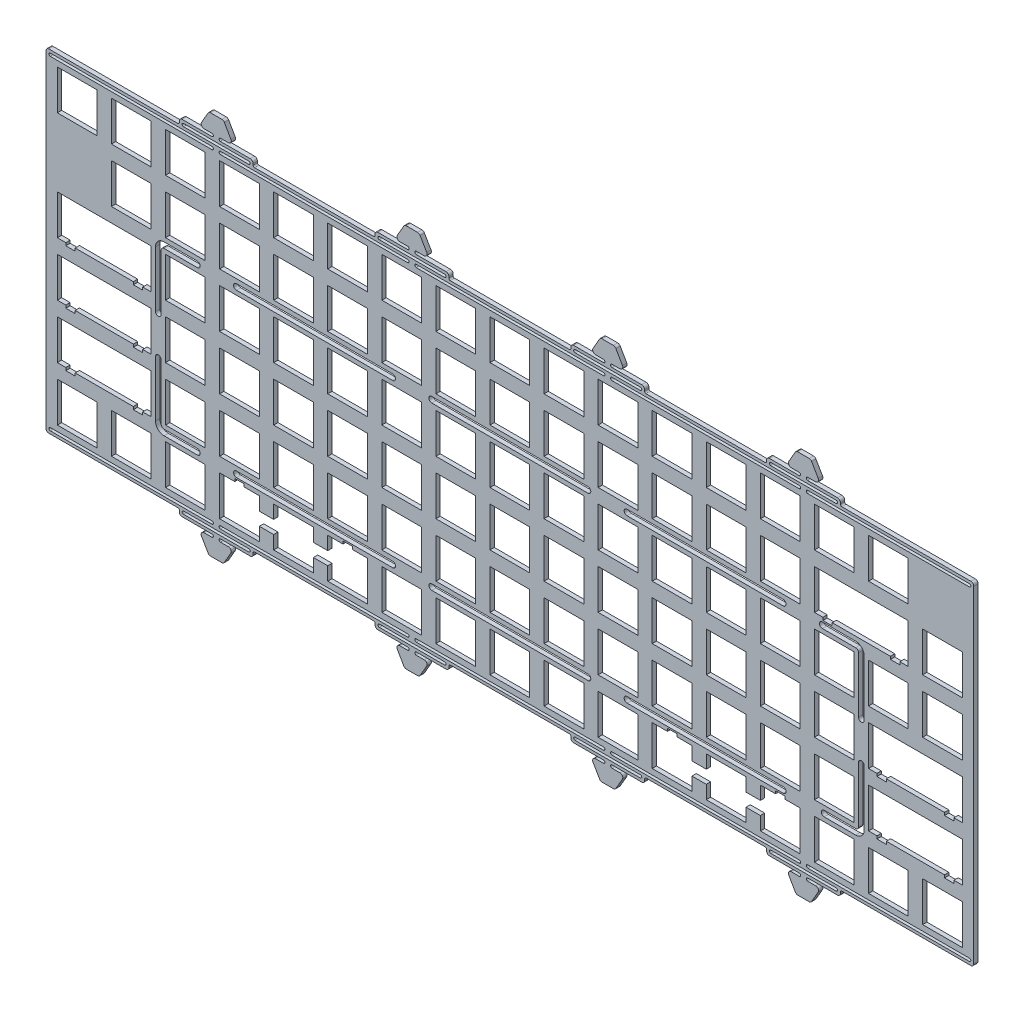
SolidWorks part; units mm, degrees
material "Acrylic (Medium-high impact)"
ref_plane "Front Plane" through (0, 0, 0) normal (0, 0, 1) x (1, 0, 0)
ref_plane "Top Plane" through (0, 0, 0) normal (0, 1, 0) x (1, 0, 0)
ref_plane "Right Plane" through (0, 0, 0) normal (1, 0, 0) x (0, 0, -1)
sketch "Sketch2" plane through (0, 0, 0) normal (0, 0, 1) x (1, 0, 0)
  line L0 (102.249, -54.6242) -> (102.249, -40.6233)
  line L1 (102.249, -40.6233) -> (96.9, -40.6233)
  line L2 (96.9, -40.6233) -> (96.9, -39.6546)
  line L3 (96.9, -39.6546) -> (93.6, -39.6546)
  line L4 (93.6, -39.6546) -> (93.6, -40.6233)
  line L5 (93.6, -40.6233) -> (88.25, -40.6233)
  line L6 (88.25, -40.6233) -> (88.25, -45.3238)
  line L7 (88.25, -45.3238) -> (83.199, -45.3238)
  line L8 (83.199, -45.3238) -> (83.199, -40.6233)
  line L9 (83.199, -40.6233) -> (69.2, -40.6233)
  line L10 (69.2, -40.6233) -> (69.2, -45.3238)
  line L11 (69.2, -45.3238) -> (64.149, -45.3238)
  line L12 (64.149, -45.3238) -> (64.149, -40.6233)
  line L13 (64.149, -40.6233) -> (58.801, -40.6233)
  line L14 (58.801, -40.6233) -> (58.801, -39.6546)
  line L15 (58.801, -39.6546) -> (55.5, -39.6546)
  line L16 (55.5, -39.6546) -> (55.5, -40.6233)
  line L17 (55.5, -40.6233) -> (50.15, -40.6233)
  line L18 (50.15, -40.6233) -> (50.15, -54.6242)
  line L19 (50.15, -54.6242) -> (64.149, -54.6242)
  line L20 (64.149, -54.6242) -> (64.149, -49.9223)
  line L21 (64.149, -49.9223) -> (69.2, -49.9223)
  line L22 (69.2, -49.9223) -> (69.2, -54.6242)
  line L23 (69.2, -54.6242) -> (83.199, -54.6242)
  line L24 (83.199, -54.6242) -> (83.199, -49.9223)
  line L25 (83.199, -49.9223) -> (88.25, -49.9223)
  line L26 (88.25, -49.9223) -> (88.25, -54.6242)
  line L27 (88.25, -54.6242) -> (102.249, -54.6242)
  line L28 (-50.1496, -54.6242) -> (-50.1496, -40.6233)
  line L29 (-50.1496, -40.6233) -> (-55.4991, -40.6233)
  line L30 (-55.4991, -40.6233) -> (-55.4991, -39.6546)
  line L31 (-55.4991, -39.6546) -> (-58.7994, -39.6546)
  line L32 (-58.7994, -39.6546) -> (-58.7994, -40.6233)
  line L33 (-58.7994, -40.6233) -> (-64.1503, -40.6233)
  line L34 (-64.1503, -40.6233) -> (-64.1503, -45.3238)
  line L35 (-64.1503, -45.3238) -> (-69.201, -45.3238)
  line L36 (-69.201, -45.3238) -> (-69.201, -40.6233)
  line L37 (-69.201, -40.6233) -> (-83.2003, -40.6233)
  line L38 (-83.2003, -40.6233) -> (-83.2003, -45.3238)
  line L39 (-83.2003, -45.3238) -> (-88.2496, -45.3238)
  line L40 (-88.2496, -45.3238) -> (-88.2496, -40.6233)
  line L41 (-88.2496, -40.6233) -> (-93.6003, -40.6233)
  line L42 (-93.6003, -40.6233) -> (-93.6003, -39.6546)
  line L43 (-93.6003, -39.6546) -> (-96.9003, -39.6546)
  line L44 (-96.9003, -39.6546) -> (-96.9003, -40.6233)
  line L45 (-96.9003, -40.6233) -> (-102.2503, -40.6233)
  line L46 (-102.2503, -40.6233) -> (-102.2503, -54.6242)
  line L47 (-102.2503, -54.6242) -> (-88.2496, -54.6242)
  line L48 (-88.2496, -54.6242) -> (-88.2496, -49.9223)
  line L49 (-88.2496, -49.9223) -> (-83.2003, -49.9223)
  line L50 (-83.2003, -49.9223) -> (-83.2003, -54.6242)
  line L51 (-83.2003, -54.6242) -> (-69.201, -54.6242)
  line L52 (-69.201, -54.6242) -> (-69.201, -49.9223)
  line L53 (-69.201, -49.9223) -> (-64.1503, -49.9223)
  line L54 (-64.1503, -49.9223) -> (-64.1503, -54.6242)
  line L55 (-64.1503, -54.6242) -> (-50.1496, -54.6242)
  line L56 (145.4, -40.6233) -> (159.399, -40.6233)
  line L57 (159.399, -40.6233) -> (159.399, -54.6242)
  line L58 (159.399, -54.6242) -> (145.4, -54.6242)
  line L59 (145.4, -54.6242) -> (145.4, -40.6233)
  line L60 (126.35, -40.6233) -> (140.349, -40.6233)
  line L61 (140.349, -40.6233) -> (140.349, -54.6242)
  line L62 (140.349, -54.6242) -> (126.35, -54.6242)
  line L63 (126.35, -54.6242) -> (126.35, -40.6233)
  line L64 (107.3, -40.6233) -> (121.299, -40.6233)
  line L65 (121.299, -40.6233) -> (121.299, -54.6242)
  line L66 (121.299, -54.6242) -> (107.3, -54.6242)
  line L67 (107.3, -54.6242) -> (107.3, -40.6233)
  line L68 (31.1, -40.6233) -> (45.099, -40.6233)
  line L69 (45.099, -40.6233) -> (45.099, -54.6242)
  line L70 (45.099, -54.6242) -> (31.1, -54.6242)
  line L71 (31.1, -54.6242) -> (31.1, -40.6233)
  line L72 (12.05, -40.6233) -> (26.049, -40.6233)
  line L73 (26.049, -40.6233) -> (26.049, -54.6242)
  line L74 (26.049, -54.6242) -> (12.05, -54.6242)
  line L75 (12.05, -54.6242) -> (12.05, -40.6233)
  line L76 (-7, -40.6233) -> (6.999, -40.6233)
  line L77 (6.999, -40.6233) -> (6.999, -54.6242)
  line L78 (6.999, -54.6242) -> (-7, -54.6242)
  line L79 (-7, -54.6242) -> (-7, -40.6233)
  line L80 (-26.05, -40.6233) -> (-12.051, -40.6233)
  line L81 (-12.051, -40.6233) -> (-12.051, -54.6242)
  line L82 (-12.051, -54.6242) -> (-26.05, -54.6242)
  line L83 (-26.05, -54.6242) -> (-26.05, -40.6233)
  line L84 (-45.102, -40.6233) -> (-31.101, -40.6233)
  line L85 (-31.101, -40.6233) -> (-31.101, -54.6242)
  line L86 (-31.101, -54.6242) -> (-45.102, -54.6242)
  line L87 (-45.102, -54.6242) -> (-45.102, -40.6233)
  line L88 (-121.3003, -40.6233) -> (-107.301, -40.6233)
  line L89 (-107.301, -40.6233) -> (-107.301, -54.6242)
  line L90 (-107.301, -54.6242) -> (-121.3003, -54.6242)
  line L91 (-121.3003, -54.6242) -> (-121.3003, -40.6233)
  line L92 (-140.3503, -40.6233) -> (-126.351, -40.6233)
  line L93 (-126.351, -40.6233) -> (-126.351, -54.6242)
  line L94 (-126.351, -54.6242) -> (-140.3503, -54.6242)
  line L95 (-140.3503, -54.6242) -> (-140.3503, -40.6233)
  line L96 (-159.4004, -40.6233) -> (-145.4008, -40.6233)
  line L97 (-145.4008, -40.6233) -> (-145.4008, -54.6242)
  line L98 (-145.4008, -54.6242) -> (-159.4004, -54.6242)
  line L99 (-159.4004, -54.6242) -> (-159.4004, -40.6233)
  line L100 (126.35, -21.5748) -> (126.35, -35.5742)
  line L101 (126.35, -35.5742) -> (129.325, -35.5742)
  line L102 (129.325, -35.5742) -> (129.325, -36.5443)
  line L103 (129.325, -36.5443) -> (132.624, -36.5443)
  line L104 (132.624, -36.5443) -> (132.624, -35.5742)
  line L105 (132.624, -35.5742) -> (153.125, -35.5742)
  line L106 (153.125, -35.5742) -> (153.125, -36.5443)
  line L107 (153.125, -36.5443) -> (156.424, -36.5443)
  line L108 (156.424, -36.5443) -> (156.424, -35.5742)
  line L109 (156.424, -35.5742) -> (159.399, -35.5742)
  line L110 (159.399, -35.5742) -> (159.399, -21.5748)
  line L111 (159.399, -21.5748) -> (126.35, -21.5748)
  line L112 (-159.4004, -21.5748) -> (-159.4004, -35.5742)
  line L113 (-159.4004, -35.5742) -> (-156.4252, -35.5742)
  line L114 (-156.4252, -35.5742) -> (-156.4252, -36.5443)
  line L115 (-156.4252, -36.5443) -> (-153.1262, -36.5443)
  line L116 (-153.1262, -36.5443) -> (-153.1262, -35.5742)
  line L117 (-153.1262, -35.5742) -> (-132.6251, -35.5742)
  line L118 (-132.6251, -35.5742) -> (-132.6251, -36.5443)
  line L119 (-132.6251, -36.5443) -> (-129.326, -36.5443)
  line L120 (-129.326, -36.5443) -> (-129.326, -35.5742)
  line L121 (-129.326, -35.5742) -> (-126.351, -35.5742)
  line L122 (-126.351, -35.5742) -> (-126.351, -21.5748)
  line L123 (-126.351, -21.5748) -> (-159.4004, -21.5748)
  line L124 (107.3, -21.5748) -> (121.299, -21.5748)
  line L125 (121.299, -21.5748) -> (121.299, -35.5742)
  line L126 (121.299, -35.5742) -> (107.3, -35.5742)
  line L127 (107.3, -35.5742) -> (107.3, -21.5748)
  line L128 (88.25, -21.5748) -> (102.249, -21.5748)
  line L129 (102.249, -21.5748) -> (102.249, -35.5742)
  line L130 (102.249, -35.5742) -> (88.25, -35.5742)
  line L131 (88.25, -35.5742) -> (88.25, -21.5748)
  line L132 (69.2, -21.5748) -> (83.199, -21.5748)
  line L133 (83.199, -21.5748) -> (83.199, -35.5742)
  line L134 (83.199, -35.5742) -> (69.2, -35.5742)
  line L135 (69.2, -35.5742) -> (69.2, -21.5748)
  line L136 (50.15, -21.5748) -> (64.149, -21.5748)
  line L137 (64.149, -21.5748) -> (64.149, -35.5742)
  line L138 (64.149, -35.5742) -> (50.15, -35.5742)
  line L139 (50.15, -35.5742) -> (50.15, -21.5748)
  line L140 (31.1, -21.5748) -> (45.099, -21.5748)
  line L141 (45.099, -21.5748) -> (45.099, -35.5742)
  line L142 (45.099, -35.5742) -> (31.1, -35.5742)
  line L143 (31.1, -35.5742) -> (31.1, -21.5748)
  line L144 (12.05, -21.5748) -> (26.049, -21.5748)
  line L145 (26.049, -21.5748) -> (26.049, -35.5742)
  line L146 (26.049, -35.5742) -> (12.05, -35.5742)
  line L147 (12.05, -35.5742) -> (12.05, -21.5748)
  line L148 (-7, -21.5748) -> (6.999, -21.5748)
  line L149 (6.999, -21.5748) -> (6.999, -35.5742)
  line L150 (6.999, -35.5742) -> (-7, -35.5742)
  line L151 (-7, -35.5742) -> (-7, -21.5748)
  line L152 (-26.05, -21.5748) -> (-12.051, -21.5748)
  line L153 (-12.051, -21.5748) -> (-12.051, -35.5742)
  line L154 (-12.051, -35.5742) -> (-26.05, -35.5742)
  line L155 (-26.05, -35.5742) -> (-26.05, -21.5748)
  line L156 (-45.102, -21.5748) -> (-31.101, -21.5748)
  line L157 (-31.101, -21.5748) -> (-31.101, -35.5742)
  line L158 (-31.101, -35.5742) -> (-45.102, -35.5742)
  line L159 (-45.102, -35.5742) -> (-45.102, -21.5748)
  line L160 (-64.1517, -21.5748) -> (-50.151, -21.5748)
  line L161 (-50.151, -21.5748) -> (-50.151, -35.5742)
  line L162 (-50.151, -35.5742) -> (-64.1517, -35.5742)
  line L163 (-64.1517, -35.5742) -> (-64.1517, -21.5748)
  line L164 (-83.2003, -21.5748) -> (-69.201, -21.5748)
  line L165 (-69.201, -21.5748) -> (-69.201, -35.5742)
  line L166 (-69.201, -35.5742) -> (-83.2003, -35.5742)
  line L167 (-83.2003, -35.5742) -> (-83.2003, -21.5748)
  line L168 (-102.2503, -21.5748) -> (-88.251, -21.5748)
  line L169 (-88.251, -21.5748) -> (-88.251, -35.5742)
  line L170 (-88.251, -35.5742) -> (-102.2503, -35.5742)
  line L171 (-102.2503, -35.5742) -> (-102.2503, -21.5748)
  line L172 (-121.3003, -21.5748) -> (-107.301, -21.5748)
  line L173 (-107.301, -21.5748) -> (-107.301, -35.5742)
  line L174 (-107.301, -35.5742) -> (-121.3003, -35.5742)
  line L175 (-121.3003, -35.5742) -> (-121.3003, -21.5748)
  line L176 (126.35, -2.5247) -> (126.35, -16.524)
  line L177 (126.35, -16.524) -> (129.325, -16.524)
  line L178 (129.325, -16.524) -> (129.325, -17.4942)
  line L179 (129.325, -17.4942) -> (132.624, -17.4942)
  line L180 (132.624, -17.4942) -> (132.624, -16.524)
  line L181 (132.624, -16.524) -> (153.125, -16.524)
  line L182 (153.125, -16.524) -> (153.125, -17.4942)
  line L183 (153.125, -17.4942) -> (156.424, -17.4942)
  line L184 (156.424, -17.4942) -> (156.424, -16.524)
  line L185 (156.424, -16.524) -> (159.399, -16.524)
  line L186 (159.399, -16.524) -> (159.399, -2.5247)
  line L187 (159.399, -2.5247) -> (126.35, -2.5247)
  line L188 (-159.4004, -2.5247) -> (-159.4004, -16.524)
  line L189 (-159.4004, -16.524) -> (-156.4252, -16.524)
  line L190 (-156.4252, -16.524) -> (-156.4252, -17.4942)
  line L191 (-156.4252, -17.4942) -> (-153.1262, -17.4942)
  line L192 (-153.1262, -17.4942) -> (-153.1262, -16.524)
  line L193 (-153.1262, -16.524) -> (-132.6251, -16.524)
  line L194 (-132.6251, -16.524) -> (-132.6251, -17.4942)
  line L195 (-132.6251, -17.4942) -> (-129.326, -17.4942)
  line L196 (-129.326, -17.4942) -> (-129.326, -16.524)
  line L197 (-129.326, -16.524) -> (-126.351, -16.524)
  line L198 (-126.351, -16.524) -> (-126.351, -2.5247)
  line L199 (-126.351, -2.5247) -> (-159.4004, -2.5247)
  line L200 (107.3, -2.5247) -> (121.299, -2.5247)
  line L201 (121.299, -2.5247) -> (121.299, -16.524)
  line L202 (121.299, -16.524) -> (107.3, -16.524)
  line L203 (107.3, -16.524) -> (107.3, -2.5247)
  line L204 (88.25, -2.5247) -> (102.249, -2.5247)
  line L205 (102.249, -2.5247) -> (102.249, -16.524)
  line L206 (102.249, -16.524) -> (88.25, -16.524)
  line L207 (88.25, -16.524) -> (88.25, -2.5247)
  line L208 (69.2, -2.5247) -> (83.199, -2.5247)
  line L209 (83.199, -2.5247) -> (83.199, -16.524)
  line L210 (83.199, -16.524) -> (69.2, -16.524)
  line L211 (69.2, -16.524) -> (69.2, -2.5247)
  line L212 (50.15, -2.5247) -> (64.149, -2.5247)
  line L213 (64.149, -2.5247) -> (64.149, -16.524)
  line L214 (64.149, -16.524) -> (50.15, -16.524)
  line L215 (50.15, -16.524) -> (50.15, -2.5247)
  line L216 (31.1, -2.5247) -> (45.099, -2.5247)
  line L217 (45.099, -2.5247) -> (45.099, -16.524)
  line L218 (45.099, -16.524) -> (31.1, -16.524)
  line L219 (31.1, -16.524) -> (31.1, -2.5247)
  line L220 (12.05, -2.5247) -> (26.049, -2.5247)
  line L221 (26.049, -2.5247) -> (26.049, -16.524)
  line L222 (26.049, -16.524) -> (12.05, -16.524)
  line L223 (12.05, -16.524) -> (12.05, -2.5247)
  line L224 (-7, -2.5247) -> (6.999, -2.5247)
  line L225 (6.999, -2.5247) -> (6.999, -16.524)
  line L226 (6.999, -16.524) -> (-7, -16.524)
  line L227 (-7, -16.524) -> (-7, -2.5247)
  line L228 (-26.05, -2.5247) -> (-12.051, -2.5247)
  line L229 (-12.051, -2.5247) -> (-12.051, -16.524)
  line L230 (-12.051, -16.524) -> (-26.05, -16.524)
  line L231 (-26.05, -16.524) -> (-26.05, -2.5247)
  line L232 (-45.102, -2.5247) -> (-31.101, -2.5247)
  line L233 (-31.101, -2.5247) -> (-31.101, -16.524)
  line L234 (-31.101, -16.524) -> (-45.102, -16.524)
  line L235 (-45.102, -16.524) -> (-45.102, -2.5247)
  line L236 (-64.1517, -2.5247) -> (-50.151, -2.5247)
  line L237 (-50.151, -2.5247) -> (-50.151, -16.524)
  line L238 (-50.151, -16.524) -> (-64.1517, -16.524)
  line L239 (-64.1517, -16.524) -> (-64.1517, -2.5247)
  line L240 (-83.2003, -2.5247) -> (-69.201, -2.5247)
  line L241 (-69.201, -2.5247) -> (-69.201, -16.524)
  line L242 (-69.201, -16.524) -> (-83.2003, -16.524)
  line L243 (-83.2003, -16.524) -> (-83.2003, -2.5247)
  line L244 (-102.2503, -2.5247) -> (-88.251, -2.5247)
  line L245 (-88.251, -2.5247) -> (-88.251, -16.524)
  line L246 (-88.251, -16.524) -> (-102.2503, -16.524)
  line L247 (-102.2503, -16.524) -> (-102.2503, -2.5247)
  line L248 (-121.3003, -2.5247) -> (-107.301, -2.5247)
  line L249 (-107.301, -2.5247) -> (-107.301, -16.524)
  line L250 (-107.301, -16.524) -> (-121.3003, -16.524)
  line L251 (-121.3003, -16.524) -> (-121.3003, -2.5247)
  line L252 (-159.4004, 16.5253) -> (-159.4004, 2.526)
  line L253 (-159.4004, 2.526) -> (-156.4252, 2.526)
  line L254 (-156.4252, 2.526) -> (-156.4252, 1.5558)
  line L255 (-156.4252, 1.5558) -> (-153.1262, 1.5558)
  line L256 (-153.1262, 1.5558) -> (-153.1262, 2.526)
  line L257 (-153.1262, 2.526) -> (-132.6251, 2.526)
  line L258 (-132.6251, 2.526) -> (-132.6251, 1.5558)
  line L259 (-132.6251, 1.5558) -> (-129.326, 1.5558)
  line L260 (-129.326, 1.5558) -> (-129.326, 2.526)
  line L261 (-129.326, 2.526) -> (-126.351, 2.526)
  line L262 (-126.351, 2.526) -> (-126.351, 16.5253)
  line L263 (-126.351, 16.5253) -> (-159.4004, 16.5253)
  line L264 (145.4, 16.5253) -> (159.399, 16.5253)
  line L265 (159.399, 16.5253) -> (159.399, 2.526)
  line L266 (159.399, 2.526) -> (145.4, 2.526)
  line L267 (145.4, 2.526) -> (145.4, 16.5253)
  line L268 (126.35, 16.5253) -> (140.349, 16.5253)
  line L269 (140.349, 16.5253) -> (140.349, 2.526)
  line L270 (140.349, 2.526) -> (126.35, 2.526)
  line L271 (126.35, 2.526) -> (126.35, 16.5253)
  line L272 (107.3, 16.5253) -> (121.299, 16.5253)
  line L273 (121.299, 16.5253) -> (121.299, 2.526)
  line L274 (121.299, 2.526) -> (107.3, 2.526)
  line L275 (107.3, 2.526) -> (107.3, 16.5253)
  line L276 (88.25, 16.5253) -> (102.249, 16.5253)
  line L277 (102.249, 16.5253) -> (102.249, 2.526)
  line L278 (102.249, 2.526) -> (88.25, 2.526)
  line L279 (88.25, 2.526) -> (88.25, 16.5253)
  line L280 (69.2, 16.5253) -> (83.199, 16.5253)
  line L281 (83.199, 16.5253) -> (83.199, 2.526)
  line L282 (83.199, 2.526) -> (69.2, 2.526)
  line L283 (69.2, 2.526) -> (69.2, 16.5253)
  line L284 (50.15, 16.5253) -> (64.149, 16.5253)
  line L285 (64.149, 16.5253) -> (64.149, 2.526)
  line L286 (64.149, 2.526) -> (50.15, 2.526)
  line L287 (50.15, 2.526) -> (50.15, 16.5253)
  line L288 (31.1, 16.5253) -> (45.099, 16.5253)
  line L289 (45.099, 16.5253) -> (45.099, 2.526)
  line L290 (45.099, 2.526) -> (31.1, 2.526)
  line L291 (31.1, 2.526) -> (31.1, 16.5253)
  line L292 (12.05, 16.5253) -> (26.049, 16.5253)
  line L293 (26.049, 16.5253) -> (26.049, 2.526)
  line L294 (26.049, 2.526) -> (12.05, 2.526)
  line L295 (12.05, 2.526) -> (12.05, 16.5253)
  line L296 (-7, 16.5253) -> (6.999, 16.5253)
  line L297 (6.999, 16.5253) -> (6.999, 2.526)
  line L298 (6.999, 2.526) -> (-7, 2.526)
  line L299 (-7, 2.526) -> (-7, 16.5253)
  line L300 (-26.05, 16.5253) -> (-12.051, 16.5253)
  line L301 (-12.051, 16.5253) -> (-12.051, 2.526)
  line L302 (-12.051, 2.526) -> (-26.05, 2.526)
  line L303 (-26.05, 2.526) -> (-26.05, 16.5253)
  line L304 (-45.102, 16.5253) -> (-31.101, 16.5253)
  line L305 (-31.101, 16.5253) -> (-31.101, 2.526)
  line L306 (-31.101, 2.526) -> (-45.102, 2.526)
  line L307 (-45.102, 2.526) -> (-45.102, 16.5253)
  line L308 (-64.1517, 16.5253) -> (-50.151, 16.5253)
  line L309 (-50.151, 16.5253) -> (-50.151, 2.526)
  line L310 (-50.151, 2.526) -> (-64.1517, 2.526)
  line L311 (-64.1517, 2.526) -> (-64.1517, 16.5253)
  line L312 (-83.2003, 16.5253) -> (-69.201, 16.5253)
  line L313 (-69.201, 16.5253) -> (-69.201, 2.526)
  line L314 (-69.201, 2.526) -> (-83.2003, 2.526)
  line L315 (-83.2003, 2.526) -> (-83.2003, 16.5253)
  line L316 (-102.2503, 16.5253) -> (-88.251, 16.5253)
  line L317 (-88.251, 16.5253) -> (-88.251, 2.526)
  line L318 (-88.251, 2.526) -> (-102.2503, 2.526)
  line L319 (-102.2503, 2.526) -> (-102.2503, 16.5253)
  line L320 (-121.3003, 16.5253) -> (-107.301, 16.5253)
  line L321 (-107.301, 16.5253) -> (-107.301, 2.526)
  line L322 (-107.301, 2.526) -> (-121.3003, 2.526)
  line L323 (-121.3003, 2.526) -> (-121.3003, 16.5253)
  line L324 (107.3, 35.5753) -> (107.3, 21.576)
  line L325 (107.3, 21.576) -> (110.275, 21.576)
  line L326 (110.275, 21.576) -> (110.275, 20.6058)
  line L327 (110.275, 20.6058) -> (113.574, 20.6058)
  line L328 (113.574, 20.6058) -> (113.574, 21.576)
  line L329 (113.574, 21.576) -> (134.075, 21.576)
  line L330 (134.075, 21.576) -> (134.075, 20.6058)
  line L331 (134.075, 20.6058) -> (137.374, 20.6058)
  line L332 (137.374, 20.6058) -> (137.374, 21.576)
  line L333 (137.374, 21.576) -> (140.349, 21.576)
  line L334 (140.349, 21.576) -> (140.349, 35.5753)
  line L335 (140.349, 35.5753) -> (107.3, 35.5753)
  line L336 (145.4, 35.5753) -> (159.399, 35.5753)
  line L337 (159.399, 35.5753) -> (159.399, 21.576)
  line L338 (159.399, 21.576) -> (145.4, 21.576)
  line L339 (145.4, 21.576) -> (145.4, 35.5753)
  line L340 (88.25, 35.5753) -> (102.249, 35.5753)
  line L341 (102.249, 35.5753) -> (102.249, 21.576)
  line L342 (102.249, 21.576) -> (88.25, 21.576)
  line L343 (88.25, 21.576) -> (88.25, 35.5753)
  line L344 (69.2, 35.5753) -> (83.199, 35.5753)
  line L345 (83.199, 35.5753) -> (83.199, 21.576)
  line L346 (83.199, 21.576) -> (69.2, 21.576)
  line L347 (69.2, 21.576) -> (69.2, 35.5753)
  line L348 (50.15, 35.5753) -> (64.149, 35.5753)
  line L349 (64.149, 35.5753) -> (64.149, 21.576)
  line L350 (64.149, 21.576) -> (50.15, 21.576)
  line L351 (50.15, 21.576) -> (50.15, 35.5753)
  line L352 (31.1, 35.5753) -> (45.099, 35.5753)
  line L353 (45.099, 35.5753) -> (45.099, 21.576)
  line L354 (45.099, 21.576) -> (31.1, 21.576)
  line L355 (31.1, 21.576) -> (31.1, 35.5753)
  line L356 (12.05, 35.5753) -> (26.049, 35.5753)
  line L357 (26.049, 35.5753) -> (26.049, 21.576)
  line L358 (26.049, 21.576) -> (12.05, 21.576)
  line L359 (12.05, 21.576) -> (12.05, 35.5753)
  line L360 (-7, 35.5753) -> (6.999, 35.5753)
  line L361 (6.999, 35.5753) -> (6.999, 21.576)
  line L362 (6.999, 21.576) -> (-7, 21.576)
  line L363 (-7, 21.576) -> (-7, 35.5753)
  line L364 (-26.05, 35.5753) -> (-12.051, 35.5753)
  line L365 (-12.051, 35.5753) -> (-12.051, 21.576)
  line L366 (-12.051, 21.576) -> (-26.05, 21.576)
  line L367 (-26.05, 21.576) -> (-26.05, 35.5753)
  line L368 (-45.102, 35.5753) -> (-31.101, 35.5753)
  line L369 (-31.101, 35.5753) -> (-31.101, 21.576)
  line L370 (-31.101, 21.576) -> (-45.102, 21.576)
  line L371 (-45.102, 21.576) -> (-45.102, 35.5753)
  line L372 (-64.1517, 35.5753) -> (-50.151, 35.5753)
  line L373 (-50.151, 35.5753) -> (-50.151, 21.576)
  line L374 (-50.151, 21.576) -> (-64.1517, 21.576)
  line L375 (-64.1517, 21.576) -> (-64.1517, 35.5753)
  line L376 (-83.2003, 35.5753) -> (-69.201, 35.5753)
  line L377 (-69.201, 35.5753) -> (-69.201, 21.576)
  line L378 (-69.201, 21.576) -> (-83.2003, 21.576)
  line L379 (-83.2003, 21.576) -> (-83.2003, 35.5753)
  line L380 (-102.2503, 35.5753) -> (-88.251, 35.5753)
  line L381 (-88.251, 35.5753) -> (-88.251, 21.576)
  line L382 (-88.251, 21.576) -> (-102.2503, 21.576)
  line L383 (-102.2503, 21.576) -> (-102.2503, 35.5753)
  line L384 (-121.3003, 35.5753) -> (-107.301, 35.5753)
  line L385 (-107.301, 35.5753) -> (-107.301, 21.576)
  line L386 (-107.301, 21.576) -> (-121.3003, 21.576)
  line L387 (-121.3003, 21.576) -> (-121.3003, 35.5753)
  line L388 (-140.3503, 35.5753) -> (-126.351, 35.5753)
  line L389 (-126.351, 35.5753) -> (-126.351, 21.576)
  line L390 (-126.351, 21.576) -> (-140.3503, 21.576)
  line L391 (-140.3503, 21.576) -> (-140.3503, 35.5753)
  line L392 (126.35, 54.6252) -> (140.349, 54.6252)
  line L393 (140.349, 54.6252) -> (140.349, 40.626)
  line L394 (140.349, 40.626) -> (126.35, 40.626)
  line L395 (126.35, 40.626) -> (126.35, 54.6252)
  line L396 (107.3, 54.6252) -> (121.299, 54.6252)
  line L397 (121.299, 54.6252) -> (121.299, 40.626)
  line L398 (121.299, 40.626) -> (107.3, 40.626)
  line L399 (107.3, 40.626) -> (107.3, 54.6252)
  line L400 (88.25, 54.6252) -> (102.249, 54.6252)
  line L401 (102.249, 54.6252) -> (102.249, 40.626)
  line L402 (102.249, 40.626) -> (88.25, 40.626)
  line L403 (88.25, 40.626) -> (88.25, 54.6252)
  line L404 (69.2, 54.6252) -> (83.199, 54.6252)
  line L405 (83.199, 54.6252) -> (83.199, 40.626)
  line L406 (83.199, 40.626) -> (69.2, 40.626)
  line L407 (69.2, 40.626) -> (69.2, 54.6252)
  line L408 (50.15, 54.6252) -> (64.149, 54.6252)
  line L409 (64.149, 54.6252) -> (64.149, 40.626)
  line L410 (64.149, 40.626) -> (50.15, 40.626)
  line L411 (50.15, 40.626) -> (50.15, 54.6252)
  line L412 (31.1, 54.6252) -> (45.099, 54.6252)
  line L413 (45.099, 54.6252) -> (45.099, 40.626)
  line L414 (45.099, 40.626) -> (31.1, 40.626)
  line L415 (31.1, 40.626) -> (31.1, 54.6252)
  line L416 (12.05, 54.6252) -> (26.049, 54.6252)
  line L417 (26.049, 54.6252) -> (26.049, 40.626)
  line L418 (26.049, 40.626) -> (12.05, 40.626)
  line L419 (12.05, 40.626) -> (12.05, 54.6252)
  line L420 (-7, 54.6252) -> (6.999, 54.6252)
  line L421 (6.999, 54.6252) -> (6.999, 40.626)
  line L422 (6.999, 40.626) -> (-7, 40.626)
  line L423 (-7, 40.626) -> (-7, 54.6252)
  line L424 (-26.05, 54.6252) -> (-12.051, 54.6252)
  line L425 (-12.051, 54.6252) -> (-12.051, 40.626)
  line L426 (-12.051, 40.626) -> (-26.05, 40.626)
  line L427 (-26.05, 40.626) -> (-26.05, 54.6252)
  line L428 (-45.102, 54.6252) -> (-31.101, 54.6252)
  line L429 (-31.101, 54.6252) -> (-31.101, 40.626)
  line L430 (-31.101, 40.626) -> (-45.102, 40.626)
  line L431 (-45.102, 40.626) -> (-45.102, 54.6252)
  line L432 (-64.1517, 54.6252) -> (-50.151, 54.6252)
  line L433 (-50.151, 54.6252) -> (-50.151, 40.626)
  line L434 (-50.151, 40.626) -> (-64.1517, 40.626)
  line L435 (-64.1517, 40.626) -> (-64.1517, 54.6252)
  line L436 (-83.2003, 54.6252) -> (-69.201, 54.6252)
  line L437 (-69.201, 54.6252) -> (-69.201, 40.626)
  line L438 (-69.201, 40.626) -> (-83.2003, 40.626)
  line L439 (-83.2003, 40.626) -> (-83.2003, 54.6252)
  line L440 (-102.2503, 54.6252) -> (-88.251, 54.6252)
  line L441 (-88.251, 54.6252) -> (-88.251, 40.626)
  line L442 (-88.251, 40.626) -> (-102.2503, 40.626)
  line L443 (-102.2503, 40.626) -> (-102.2503, 54.6252)
  line L444 (-121.3003, 54.6252) -> (-107.301, 54.6252)
  line L445 (-107.301, 54.6252) -> (-107.301, 40.626)
  line L446 (-107.301, 40.626) -> (-121.3003, 40.626)
  line L447 (-121.3003, 40.626) -> (-121.3003, 54.6252)
  line L448 (-140.3503, 54.6252) -> (-126.351, 54.6252)
  line L449 (-126.351, 54.6252) -> (-126.351, 40.626)
  line L450 (-126.351, 40.626) -> (-140.3503, 40.626)
  line L451 (-140.3503, 40.626) -> (-140.3503, 54.6252)
  line L452 (-159.4004, 54.6252) -> (-145.4008, 54.6252)
  line L453 (-145.4008, 54.6252) -> (-145.4008, 40.626)
  line L454 (-145.4008, 40.626) -> (-159.4004, 40.626)
  line L455 (-159.4004, 40.626) -> (-159.4004, 54.6252)
  line L456 (-162.4006, -55.6246) -> (-162.4006, 55.6256) construction
  line L457 (-160.4006, 57.6256) -> (160.3992, 57.6256) construction
  line L458 (162.3992, 55.6256) -> (162.3992, -55.6246) construction
  line L459 (160.3992, -57.6246) -> (-160.4006, -57.6246) construction
  line L461 (-172.4004, 67.6252) -> (172.399, 67.6252)
  line L462 (-172.4004, 67.6252) -> (-172.4004, -67.6242)
  line L463 (-172.4004, -67.6242) -> (172.399, -67.6242)
  line L464 (172.399, 67.6252) -> (172.399, -67.6242)
  circle A0 centre (-152.4006, 47.6256) radius 2 construction
  circle A1 centre (-133.3508, 47.6256) radius 2 construction
  circle A2 centre (-114.3008, 47.6256) radius 2 construction
  circle A3 centre (-95.2508, 47.6256) radius 2 construction
  circle A4 centre (-76.2008, 47.6256) radius 2 construction
  circle A5 centre (-57.1508, 47.6256) radius 2 construction
  circle A6 centre (-38.1008, 47.6256) radius 2 construction
  circle A7 centre (-19.0508, 47.6256) radius 2 construction
  circle A8 centre (-0.0008, 47.6256) radius 2 construction
  circle A9 centre (19.0492, 47.6256) radius 2 construction
  circle A10 centre (38.0992, 47.6256) radius 2 construction
  circle A11 centre (57.1492, 47.6256) radius 2 construction
  circle A12 centre (76.1992, 47.6256) radius 2 construction
  circle A13 centre (95.2492, 47.6256) radius 2 construction
  circle A14 centre (114.2992, 47.6256) radius 2 construction
  circle A15 centre (133.3492, 47.6256) radius 2 construction
  circle A16 centre (152.3992, 28.5756) radius 2 construction
  circle A17 centre (133.3492, 28.5756) radius 2 construction
  circle A18 centre (95.2492, 28.5756) radius 2 construction
  circle A19 centre (152.3992, 9.5256) radius 2 construction
  circle A20 centre (133.3492, 9.5256) radius 2 construction
  circle A21 centre (114.2992, 9.5256) radius 2 construction
  circle A22 centre (95.2492, 9.5256) radius 2 construction
  circle A23 centre (76.1992, 9.5256) radius 2 construction
  circle A24 centre (76.1992, 28.5756) radius 2 construction
  circle A25 centre (57.1492, 28.5756) radius 2 construction
  circle A26 centre (57.1492, 9.5256) radius 2 construction
  circle A27 centre (38.0992, 28.5756) radius 2 construction
  circle A28 centre (19.0492, 28.5756) radius 2 construction
  circle A29 centre (-0.0008, 28.5756) radius 2 construction
  circle A30 centre (-19.0508, 28.5756) radius 2 construction
  circle A31 centre (-38.1008, 28.5756) radius 2 construction
  circle A32 centre (-57.1508, 28.5756) radius 2 construction
  circle A33 centre (-76.2008, 28.5756) radius 2 construction
  circle A34 centre (-95.2508, 28.5756) radius 2 construction
  circle A35 centre (-114.3008, 28.5756) radius 2 construction
  circle A36 centre (-133.3508, 28.5756) radius 2 construction
  circle A37 centre (-133.3508, 9.5256) radius 2 construction
  circle A38 centre (-114.3008, 9.5256) radius 2 construction
  circle A39 centre (-133.3508, -9.5244) radius 2 construction
  circle A40 centre (-95.2508, 9.5256) radius 2 construction
  circle A41 centre (-76.2008, 9.5256) radius 2 construction
  circle A42 centre (-57.1508, 9.5256) radius 2 construction
  circle A43 centre (-38.1008, 9.5256) radius 2 construction
  circle A44 centre (-19.0508, 9.5256) radius 2 construction
  circle A45 centre (-0.0008, 9.5256) radius 2 construction
  circle A46 centre (19.0492, 9.5256) radius 2 construction
  circle A47 centre (38.0992, 9.5256) radius 2 construction
  circle A48 centre (152.3992, -9.5244) radius 2 construction
  circle A49 centre (152.3992, -28.5746) radius 2 construction
  circle A50 centre (152.3992, -47.6246) radius 2 construction
  circle A51 centre (133.3492, -47.6246) radius 2 construction
  circle A52 centre (114.2992, -47.6246) radius 2 construction
  circle A53 centre (95.2492, -47.6246) radius 2 construction
  circle A54 centre (114.2992, -28.5746) radius 2 construction
  circle A55 centre (95.2492, -28.5746) radius 2 construction
  circle A56 centre (76.1992, -47.6246) radius 2 construction
  circle A57 centre (57.1492, -47.6246) radius 2 construction
  circle A58 centre (57.1492, -28.5746) radius 2 construction
  circle A59 centre (57.1492, -9.5244) radius 2 construction
  circle A60 centre (76.1992, -9.5244) radius 2 construction
  circle A61 centre (76.1992, -28.5746) radius 2 construction
  circle A62 centre (95.2492, -9.5244) radius 2 construction
  circle A63 centre (114.2992, -9.5244) radius 2 construction
  circle A64 centre (38.0992, -9.5244) radius 2 construction
  circle A65 centre (38.0992, -28.5746) radius 2 construction
  circle A66 centre (38.0992, -47.6246) radius 2 construction
  circle A67 centre (19.0492, -28.5746) radius 2 construction
  circle A68 centre (19.0492, -9.5244) radius 2 construction
  circle A69 centre (19.0492, -47.6246) radius 2 construction
  circle A70 centre (-0.0008, -9.5244) radius 2 construction
  circle A71 centre (-19.0508, -9.5244) radius 2 construction
  circle A72 centre (-19.0508, -28.5746) radius 2 construction
  circle A73 centre (-0.0008, -28.5746) radius 2 construction
  circle A74 centre (-0.0008, -47.6246) radius 2 construction
  circle A75 centre (-19.0508, -47.6246) radius 2 construction
  circle A76 centre (-38.1008, -28.5746) radius 2 construction
  circle A77 centre (-38.1008, -9.5244) radius 2 construction
  circle A78 centre (-57.1508, -9.5244) radius 2 construction
  circle A79 centre (-38.1008, -47.6246) radius 2 construction
  circle A80 centre (-57.1494, -47.6246) radius 2 construction
  circle A81 centre (-57.1508, -28.5746) radius 2 construction
  circle A82 centre (-76.2008, -47.6246) radius 2 construction
  circle A83 centre (-76.2008, -28.5746) radius 2 construction
  circle A84 centre (-76.2008, -9.5244) radius 2 construction
  circle A85 centre (-95.2508, -9.5244) radius 2 construction
  circle A86 centre (-95.2508, -28.5746) radius 2 construction
  circle A87 centre (-95.2508, -47.6246) radius 2 construction
  circle A88 centre (-114.3008, -47.6246) radius 2 construction
  circle A89 centre (-114.3008, -28.5746) radius 2 construction
  circle A90 centre (-114.3008, -9.5244) radius 2 construction
  circle A91 centre (-133.3508, -28.5746) radius 2 construction
  circle A92 centre (-133.3508, -47.6246) radius 2 construction
  circle A93 centre (-152.4006, -47.6246) radius 2 construction
  circle A94 centre (-152.4006, 9.5256) radius 2 construction
  circle A95 centre (-152.4006, -9.5244) radius 2 construction
  circle A96 centre (-152.4006, -28.5746) radius 2 construction
  circle A97 centre (133.3497, -28.5746) radius 2 construction
  circle A98 centre (133.3497, -9.5244) radius 2 construction
  circle A99 centre (114.2997, 28.5756) radius 2 construction
  circle A100 centre (-142.8757, 9.5257) radius 2 construction
  circle A101 centre (-142.8757, -9.5243) radius 2 construction
  circle A102 centre (-142.8757, -28.5744) radius 2 construction
  circle A103 centre (142.8745, -28.5744) radius 2 construction
  circle A104 centre (142.8745, -9.5243) radius 2 construction
  circle A105 centre (123.8245, 28.5757) radius 2 construction
  arc A106 (-160.4006, 57.6256) -> (-162.4006, 55.6256) centre (-160.4006, 55.6256) ccw construction
  arc A107 (162.3992, 55.6256) -> (160.3992, 57.6256) centre (160.3992, 55.6256) ccw construction
  arc A108 (160.3992, -57.6246) -> (162.3992, -55.6246) centre (160.3992, -55.6246) ccw construction
  arc A109 (-162.4006, -55.6246) -> (-160.4006, -57.6246) centre (-160.4006, -55.6246) ccw construction
  point P680 (0, 0)
  dimension "D1" = 4
  dimension "D2" = 6.999
  dimension "D3" = 12.05
  dimension "D4" = 19.0492
  dimension "D5" = 26.049
  dimension "D6" = 31.1
  dimension "D7" = 38.0992
  dimension "D8" = 50.15
  dimension "D9" = 55.5
  dimension "D10" = 57.1492
  dimension "D11" = 58.801
  dimension "D12" = 69.2
  dimension "D13" = 76.1992
  dimension "D14" = 95.2492
  dimension "D15" = 96.9
  dimension "D16" = 107.3
  dimension "D17" = 110.275
  dimension "D18" = 113.574
  dimension "D19" = 114.2992
  dimension "D20" = 114.2997
  dimension "D21" = 123.8245
  dimension "D22" = 133.3492
  dimension "D23" = 133.3497
  dimension "D24" = 134.075
  dimension "D25" = 142.8745
  dimension "D26" = 152.3992
  dimension "D27" = 162.3992
  dimension "D28" = 0.0008
  dimension "D29" = 12.051
  dimension "D30" = 19.0508
  dimension "D31" = 31.101
  dimension "D32" = 38.1008
  dimension "D33" = 45.102
  dimension "D34" = 50.1496
  dimension "D35" = 50.151
  dimension "D36" = 55.4991
  dimension "D37" = 57.1494
  dimension "D38" = 57.1508
  dimension "D39" = 58.7994
  dimension "D40" = 64.1503
  dimension "D41" = 69.201
  dimension "D42" = 76.2008
  dimension "D43" = 83.2003
  dimension "D44" = 88.2496
  dimension "D45" = 95.2508
  dimension "D46" = 107.301
  dimension "D47" = 114.3008
  dimension "D48" = 126.351
  dimension "D49" = 132.6251
  dimension "D50" = 133.3508
  dimension "D51" = 142.8757
  dimension "D52" = 145.4008
  dimension "D53" = 152.4006
  dimension "D54" = 153.1262
  dimension "D55" = 159.4004
  dimension "D56" = 162.4006
  dimension "D57" = 1.5558
  dimension "D58" = 2.526
  dimension "D59" = 9.5256
  dimension "D60" = 9.5257
  dimension "D61" = 20.6058
  dimension "D62" = 28.5756
  dimension "D63" = 28.5757
  dimension "D64" = 40.626
  dimension "D65" = 47.6256
  dimension "D66" = 54.6252
  dimension "D67" = 57.6256
  dimension "D68" = 2.5247
  dimension "D69" = 9.5243
  dimension "D70" = 9.5244
  dimension "D71" = 21.5748
  dimension "D72" = 28.5744
  dimension "D73" = 28.5746
  dimension "D74" = 35.5742
  dimension "D75" = 39.6546
  dimension "D76" = 40.6233
  dimension "D77" = 45.3238
  dimension "D78" = 47.6246
  dimension "D79" = 49.9223
  dimension "D80" = 54.6242
  dimension "D81" = 57.6246
  dimension "D82" = 0.9701
  dimension "D83" = 172.399
  dimension "D84" = 67.6242
  dimension "D86" = 172.4004
  dimension "D87" = 67.6252
extrude "Boss-Extrude1" add sketch "Sketch2" along normal blind 1.524
sketch "Sketch3" plane through (0, 0, 1.524) normal (0, 0, 1) x (1, 0, 0)
  line L0 (-172.4004, -67.6242) -> (172.399, -67.6242) construction
  line L1 (-172.4004, -67.6242) -> (-103.4405, -67.6242) construction
  line L2 (-114.9405, -59.6242) -> (-91.9405, -59.6242)
  line L3 (-34.4807, -67.6242) -> (34.4792, -67.6242) construction
  line L4 (34.4792, -67.6242) -> (103.4391, -67.6242) construction
  line L5 (103.4391, -67.6242) -> (172.399, -67.6242) construction
  line L6 (-103.4405, -67.6242) -> (-103.4405, 85.065) construction
  line L7 (-34.4807, -67.6242) -> (-34.4807, 85.065) construction
  line L8 (34.4792, -67.6242) -> (34.4792, 85.065) construction
  line L9 (103.4391, -67.6242) -> (103.4391, 85.065) construction
  line L10 (-114.9405, -58.6242) -> (-91.9405, -58.6242)
  line L11 (-106.3065, -67.1242) -> (-108.6159, -63.1242)
  line L12 (-107.7499, -61.6242) -> (-104.9405, -61.6242)
  line L13 (-104.9405, -60.6242) -> (-115.4405, -60.6242)
  line L14 (-116.4405, -59.6242) -> (-116.4405, -59.1242)
  line L15 (-116.9405, -58.6242) -> (-137.9205, -58.6242)
  line L16 (-103.4405, -67.6242) -> (-34.4807, -67.6242) construction
  line L17 (-103.4405, -55.7341) -> (-172.4004, -55.7341) construction
  line L18 (-172.4004, 67.6252) -> (-172.4004, -67.6242) construction
  line L19 (-137.9205, -55.7341) -> (-137.9205, -67.6242) construction
  line L20 (-116.4405, -58.6242) -> (-137.9205, -58.6242) construction
  line L21 (-34.4807, -56.8321) -> (34.4792, -56.8321) construction
  line L25 (-103.4405, -58.6242) -> (-103.4405, -59.6242) construction
  line L26 (-105.4405, -67.6242) -> (-101.4405, -67.6242)
  line L27 (-100.5745, -67.1242) -> (-98.2651, -63.1242)
  line L28 (-99.1311, -61.6242) -> (-101.9405, -61.6242)
  line L29 (-101.9405, -60.6242) -> (-91.4405, -60.6242)
  line L30 (-90.4405, -59.6242) -> (-90.4405, -59.1242)
  line L31 (-89.9405, -58.6242) -> (-68.9606, -58.6242)
  line L32 (-47.9806, -58.6242) -> (-68.9606, -58.6242)
  line L33 (-47.4807, -59.6242) -> (-47.4807, -59.1242)
  line L34 (-35.9807, -60.6242) -> (-46.4807, -60.6242)
  line L35 (-45.9807, -59.6242) -> (-22.9807, -59.6242)
  line L36 (-38.7901, -61.6242) -> (-35.9807, -61.6242)
  line L37 (-37.3467, -67.1242) -> (-39.6561, -63.1242)
  line L38 (-36.4807, -67.6242) -> (-32.4807, -67.6242)
  line L39 (-31.6146, -67.1242) -> (-29.3052, -63.1242)
  line L40 (-30.1713, -61.6242) -> (-32.9807, -61.6242)
  line L41 (-32.9807, -60.6242) -> (-22.4807, -60.6242)
  line L42 (-21.4807, -59.6242) -> (-21.4807, -59.1242)
  line L43 (-20.9807, -58.6242) -> (-0.0007, -58.6242)
  line L44 (20.9792, -58.6242) -> (-0.0007, -58.6242)
  line L45 (21.4792, -59.6242) -> (21.4792, -59.1242)
  line L46 (32.9792, -60.6242) -> (22.4792, -60.6242)
  line L47 (22.9792, -59.6242) -> (45.9792, -59.6242)
  line L48 (30.1698, -61.6242) -> (32.9792, -61.6242)
  line L49 (31.6132, -67.1242) -> (29.3038, -63.1242)
  line L50 (32.4792, -67.6242) -> (36.4792, -67.6242)
  line L51 (37.3452, -67.1242) -> (39.6546, -63.1242)
  line L52 (38.7886, -61.6242) -> (35.9792, -61.6242)
  line L53 (35.9792, -60.6242) -> (46.4792, -60.6242)
  line L54 (47.4792, -59.6242) -> (47.4792, -59.1242)
  line L55 (47.9792, -58.6242) -> (68.9592, -58.6242)
  line L56 (89.9391, -58.6242) -> (68.9592, -58.6242)
  line L57 (90.4391, -59.6242) -> (90.4391, -59.1242)
  line L58 (101.9391, -60.6242) -> (91.4391, -60.6242)
  line L59 (91.9391, -59.6242) -> (114.9391, -59.6242)
  line L60 (99.1297, -61.6242) -> (101.9391, -61.6242)
  line L61 (100.5731, -67.1242) -> (98.2637, -63.1242)
  line L62 (101.4391, -67.6242) -> (105.4391, -67.6242)
  line L63 (106.3051, -67.1242) -> (108.6145, -63.1242)
  line L64 (107.7485, -61.6242) -> (104.9391, -61.6242)
  line L65 (104.9391, -60.6242) -> (115.4391, -60.6242)
  line L66 (116.4391, -59.6242) -> (116.4391, -59.1242)
  line L67 (116.9391, -58.6242) -> (137.919, -58.6242)
  line L68 (0, 0) -> (-214.8315, 0) construction
  line L69 (-45.9807, -58.6242) -> (-22.9807, -58.6242)
  line L70 (22.9792, -58.6242) -> (45.9792, -58.6242)
  line L71 (91.9391, -58.6242) -> (114.9391, -58.6242)
  line L72 (-137.9205, -58.6242) -> (-162.4004, -58.6242)
  line L73 (-0.0007, -67.6242) -> (-0.0007, 88.9307) construction
  line L74 (-152.7669, -58.6242) -> (-152.7669, -67.6242) construction
  line L75 (-163.4004, -47.018) -> (-172.4004, -47.018) construction
  line L76 (163.399, -57.6242) -> (163.399, 57.6242)
  line L77 (137.919, -58.6242) -> (162.399, -58.6242)
  line L78 (-163.4004, 47.018) -> (-172.4004, 47.018) construction
  line L79 (-163.4004, -57.6242) -> (-163.4004, 57.6242)
  line L80 (-152.7669, 58.6242) -> (-152.7669, 67.6242) construction
  line L81 (-103.4405, 58.6242) -> (-103.4405, 59.6242) construction
  line L82 (-34.4807, 56.8321) -> (34.4792, 56.8321) construction
  line L83 (-116.4405, 58.6242) -> (-137.9205, 58.6242) construction
  line L84 (-137.9205, 55.7341) -> (-137.9205, 67.6242) construction
  line L85 (-103.4405, 55.7341) -> (-172.4004, 55.7341) construction
  line L86 (-103.4405, 67.6242) -> (-34.4807, 67.6242) construction
  line L87 (34.4792, 67.6242) -> (103.4391, 67.6242) construction
  line L88 (-34.4807, 67.6242) -> (34.4792, 67.6242) construction
  line L89 (-172.4004, 67.6242) -> (-103.4405, 67.6242) construction
  line L90 (137.919, 58.6242) -> (162.399, 58.6242)
  line L91 (-137.9205, 58.6242) -> (-162.4004, 58.6242)
  line L92 (91.9391, 58.6242) -> (114.9391, 58.6242)
  line L93 (22.9792, 58.6242) -> (45.9792, 58.6242)
  line L94 (-45.9807, 58.6242) -> (-22.9807, 58.6242)
  line L95 (116.9391, 58.6242) -> (137.919, 58.6242)
  line L96 (116.4391, 59.6242) -> (116.4391, 59.1242)
  line L97 (104.9391, 60.6242) -> (115.4391, 60.6242)
  line L98 (107.7485, 61.6242) -> (104.9391, 61.6242)
  line L99 (106.3051, 67.1242) -> (108.6145, 63.1242)
  line L100 (101.4391, 67.6242) -> (105.4391, 67.6242)
  line L101 (100.5731, 67.1242) -> (98.2637, 63.1242)
  line L102 (99.1297, 61.6242) -> (101.9391, 61.6242)
  line L103 (91.9391, 59.6242) -> (114.9391, 59.6242)
  line L104 (101.9391, 60.6242) -> (91.4391, 60.6242)
  line L105 (90.4391, 59.6242) -> (90.4391, 59.1242)
  line L106 (89.9391, 58.6242) -> (68.9592, 58.6242)
  line L107 (47.9792, 58.6242) -> (68.9592, 58.6242)
  line L108 (47.4792, 59.6242) -> (47.4792, 59.1242)
  line L109 (35.9792, 60.6242) -> (46.4792, 60.6242)
  line L110 (38.7886, 61.6242) -> (35.9792, 61.6242)
  line L111 (37.3452, 67.1242) -> (39.6546, 63.1242)
  line L112 (32.4792, 67.6242) -> (36.4792, 67.6242)
  line L113 (31.6132, 67.1242) -> (29.3038, 63.1242)
  line L114 (30.1698, 61.6242) -> (32.9792, 61.6242)
  line L115 (22.9792, 59.6242) -> (45.9792, 59.6242)
  line L116 (32.9792, 60.6242) -> (22.4792, 60.6242)
  line L117 (21.4792, 59.6242) -> (21.4792, 59.1242)
  line L118 (20.9792, 58.6242) -> (-0.0007, 58.6242)
  line L119 (-20.9807, 58.6242) -> (-0.0007, 58.6242)
  line L120 (-21.4807, 59.6242) -> (-21.4807, 59.1242)
  line L121 (-32.9807, 60.6242) -> (-22.4807, 60.6242)
  line L122 (-30.1713, 61.6242) -> (-32.9807, 61.6242)
  line L123 (-31.6146, 67.1242) -> (-29.3052, 63.1242)
  line L124 (-36.4807, 67.6242) -> (-32.4807, 67.6242)
  line L125 (-37.3467, 67.1242) -> (-39.6561, 63.1242)
  line L126 (-38.7901, 61.6242) -> (-35.9807, 61.6242)
  line L127 (-45.9807, 59.6242) -> (-22.9807, 59.6242)
  line L128 (-35.9807, 60.6242) -> (-46.4807, 60.6242)
  line L129 (-47.4807, 59.6242) -> (-47.4807, 59.1242)
  line L130 (-47.9806, 58.6242) -> (-68.9606, 58.6242)
  line L131 (-89.9405, 58.6242) -> (-68.9606, 58.6242)
  line L132 (-90.4405, 59.6242) -> (-90.4405, 59.1242)
  line L133 (-101.9405, 60.6242) -> (-91.4405, 60.6242)
  line L134 (-99.1311, 61.6242) -> (-101.9405, 61.6242)
  line L135 (-100.5745, 67.1242) -> (-98.2651, 63.1242)
  line L136 (-105.4405, 67.6242) -> (-101.4405, 67.6242)
  line L137 (-116.9405, 58.6242) -> (-137.9205, 58.6242)
  line L138 (-116.4405, 59.6242) -> (-116.4405, 59.1242)
  line L139 (-104.9405, 60.6242) -> (-115.4405, 60.6242)
  line L140 (-107.7499, 61.6242) -> (-104.9405, 61.6242)
  line L141 (-106.3065, 67.1242) -> (-108.6159, 63.1242)
  line L142 (-114.9405, 58.6242) -> (-91.9405, 58.6242)
  line L143 (-114.9405, 59.6242) -> (-91.9405, 59.6242)
  line L144 (-101.9405, -57.1242) -> (-35.9807, -57.1242) construction
  line L149 (-101.9405, -57.6242) -> (-35.9807, -57.6242)
  line L150 (-101.9405, -56.6242) -> (-35.9807, -56.6242)
  line L151 (-68.9606, -58.6242) -> (-68.9606, 83.749) construction
  line L152 (68.9592, -58.6242) -> (68.9592, 77.0116) construction
  line L153 (-32.9807, -56.6242) -> (32.9792, -56.6242)
  line L154 (-32.9807, -57.6242) -> (32.9792, -57.6242)
  line L155 (35.9792, -56.6242) -> (101.9391, -56.6242)
  line L156 (35.9792, -57.6242) -> (101.9391, -57.6242)
  line L157 (-161.9046, -57.1242) -> (-104.9405, -57.1242) construction
  line L158 (-161.9046, -57.6242) -> (-104.9405, -57.6242)
  line L159 (-161.9046, -56.6242) -> (-104.9405, -56.6242)
  line L160 (161.9031, -56.6242) -> (104.9391, -56.6242)
  line L161 (161.9031, -57.6242) -> (104.9391, -57.6242)
  line L162 (161.9031, 57.6242) -> (104.9391, 57.6242)
  line L163 (161.9031, 56.6242) -> (104.9391, 56.6242)
  line L164 (35.9792, 57.6242) -> (101.9391, 57.6242)
  line L165 (35.9792, 56.6242) -> (101.9391, 56.6242)
  line L166 (-32.9807, 57.6242) -> (32.9792, 57.6242)
  line L167 (-32.9807, 56.6242) -> (32.9792, 56.6242)
  line L168 (-101.9405, 56.6242) -> (-35.9807, 56.6242)
  line L169 (-101.9405, 57.6242) -> (-35.9807, 57.6242)
  line L170 (-161.9046, 56.6242) -> (-104.9405, 56.6242)
  line L171 (-161.9046, 57.6242) -> (-104.9405, 57.6242)
  line L172 (-121.3003, 21.576) -> (-107.301, 21.576) construction
  line L173 (-123.8257, 19.0506) -> (-110.0674, 19.0506) construction
  line L174 (-123.8257, 19.0506) -> (-123.8257, 4.7633) construction
  line L175 (-123.8257, -38.0988) -> (-110.0674, -38.0988) construction
  line L176 (123.8245, 19.0506) -> (123.8245, 4.7633) construction
  line L177 (121.299, 2.526) -> (121.299, 16.5253) construction
  line L178 (126.35, 16.5253) -> (126.35, 2.526) construction
  line L179 (-107.301, -40.6233) -> (-121.3003, -40.6233) construction
  line L180 (-121.3003, -35.5742) -> (-107.301, -35.5742) construction
  line L181 (-121.3003, 16.5253) -> (-121.3003, 2.526) construction
  line L182 (-126.351, 2.526) -> (-126.351, 16.5253) construction
  line L183 (-107.301, 16.5253) -> (-121.3003, 16.5253) construction
  line L184 (121.299, 2.526) -> (121.299, 16.5253) construction
  line L185 (126.35, 16.5253) -> (126.35, 2.526) construction
  line L186 (-107.301, -40.6233) -> (-121.3003, -40.6233) construction
  line L187 (-121.3003, -35.5742) -> (-107.301, -35.5742) construction
  line L188 (-121.3003, 16.5253) -> (-121.3003, 2.526) construction
  line L189 (-126.351, 2.526) -> (-126.351, 16.5253) construction
  line L190 (-107.301, 16.5253) -> (-121.3003, 16.5253) construction
  line L191 (-121.3003, 21.576) -> (-107.301, 21.576) construction
  line L192 (123.8245, 4.7633) -> (123.8245, -9.5241) construction
  line L193 (123.8245, -9.5241) -> (123.8245, -23.8114) construction
  line L194 (123.8245, -23.8114) -> (123.8245, -38.0988) construction
  line L195 (-123.8257, 4.7633) -> (-123.8257, -9.5241) construction
  line L196 (-123.8257, -9.5241) -> (-123.8257, -23.8114) construction
  line L197 (-123.8257, -23.8114) -> (-123.8257, -38.0988) construction
  line L198 (-110.0674, 19.0506) -> (-96.309, 19.0506) construction
  line L199 (-96.309, 19.0506) -> (-82.5507, 19.0506) construction
  line L200 (-82.5507, 19.0506) -> (-68.7923, 19.0506) construction
  line L201 (-68.7923, 19.0506) -> (-55.034, 19.0506) construction
  line L202 (-55.034, 19.0506) -> (-41.2756, 19.0506) construction
  line L203 (-41.2756, 19.0506) -> (-27.5173, 19.0506) construction
  line L204 (-27.5173, 19.0506) -> (-13.759, 19.0506) construction
  line L205 (-13.759, 19.0506) -> (-0.0006, 19.0506) construction
  line L206 (-0.0006, 19.0506) -> (13.7577, 19.0506) construction
  line L207 (13.7577, 19.0506) -> (27.5161, 19.0506) construction
  line L208 (27.5161, 19.0506) -> (41.2744, 19.0506) construction
  line L209 (41.2744, 19.0506) -> (55.0327, 19.0506) construction
  line L210 (55.0327, 19.0506) -> (68.7911, 19.0506) construction
  line L211 (68.7911, 19.0506) -> (82.5494, 19.0506) construction
  line L212 (82.5494, 19.0506) -> (96.3078, 19.0506) construction
  line L213 (96.3078, 19.0506) -> (110.0661, 19.0506) construction
  line L214 (110.0661, 19.0506) -> (123.8245, 19.0506) construction
  line L215 (-123.8257, -36.0988) -> (-123.8257, -16.4041) construction
  line L216 (-27.5173, 19.0506) -> (27.5161, 19.0506) construction
  line L217 (-96.309, 19.0506) -> (-41.2756, 19.0506) construction
  line L218 (41.2744, 19.0506) -> (96.3078, 19.0506) construction
  line L219 (-110.0674, -38.0988) -> (-96.309, -38.0988) construction
  line L220 (-96.309, -38.0988) -> (-82.5507, -38.0988) construction
  line L221 (-82.5507, -38.0988) -> (-68.7923, -38.0988) construction
  line L222 (-68.7923, -38.0988) -> (-55.034, -38.0988) construction
  line L223 (-55.034, -38.0988) -> (-41.2756, -38.0988) construction
  line L224 (-41.2756, -38.0988) -> (-27.5173, -38.0988) construction
  line L225 (-27.5173, -38.0988) -> (-13.759, -38.0988) construction
  line L226 (-13.759, -38.0988) -> (-0.0006, -38.0988) construction
  line L227 (-0.0006, -38.0988) -> (13.7577, -38.0988) construction
  line L228 (13.7577, -38.0988) -> (27.5161, -38.0988) construction
  line L229 (27.5161, -38.0988) -> (41.2744, -38.0988) construction
  line L230 (41.2744, -38.0988) -> (55.0327, -38.0988) construction
  line L231 (55.0327, -38.0988) -> (68.7911, -38.0988) construction
  line L232 (68.7911, -38.0988) -> (82.5494, -38.0988) construction
  line L233 (82.5494, -38.0988) -> (96.3078, -38.0988) construction
  line L234 (96.3078, -38.0988) -> (110.0661, -38.0988) construction
  line L235 (110.0661, -38.0988) -> (123.8245, -38.0988) construction
  line L236 (-96.309, -38.0988) -> (-41.2756, -38.0988) construction
  line L237 (-27.5173, -38.0988) -> (27.5161, -38.0988) construction
  line L238 (41.2744, -38.0988) -> (96.3078, -38.0988) construction
  line L239 (-110.0674, 19.0506) -> (-121.8257, 19.0506) construction
  line L240 (-123.8257, 17.0506) -> (-123.8257, -2.6441) construction
  line L241 (-121.8257, -38.0988) -> (-110.0674, -38.0988) construction
  line L242 (110.7182, -38.0988) -> (121.8245, -38.0988) construction
  line L243 (123.8245, 17.0506) -> (123.8245, -2.6441) construction
  line L244 (123.8245, -36.0988) -> (123.8245, -16.4041) construction
  line L245 (121.8245, 19.0506) -> (110.0661, 19.0506) construction
  line L246 (-121.8257, -37.0988) -> (-110.0674, -37.0988)
  line L247 (-122.8257, -36.0988) -> (-122.8257, -16.4041)
  line L248 (-27.5173, 18.0506) -> (27.5161, 18.0506)
  line L249 (-96.309, 18.0506) -> (-41.2756, 18.0506)
  line L250 (41.2744, 18.0506) -> (96.3078, 18.0506)
  line L251 (-96.309, -39.0988) -> (-41.2756, -39.0988)
  line L252 (-27.5173, -39.0988) -> (27.5161, -39.0988)
  line L253 (41.2744, -39.0988) -> (96.3078, -39.0988)
  line L254 (-110.0674, 20.0506) -> (-121.8257, 20.0506)
  line L255 (-124.8257, 17.0506) -> (-124.8257, -2.6441)
  line L256 (110.7182, -39.0988) -> (121.8245, -39.0988)
  line L257 (124.8245, -36.0988) -> (124.8245, -16.4041)
  line L258 (121.8245, 18.0506) -> (110.0661, 18.0506)
  line L259 (122.8245, 17.0506) -> (122.8245, -2.6441)
  line L260 (-121.8257, -39.0988) -> (-110.0674, -39.0988)
  line L261 (-124.8257, -36.0988) -> (-124.8257, -16.4041)
  line L262 (-27.5173, 20.0506) -> (27.5161, 20.0506)
  line L263 (-96.309, 20.0506) -> (-41.2756, 20.0506)
  line L264 (41.2744, 20.0506) -> (96.3078, 20.0506)
  line L265 (-96.309, -37.0988) -> (-41.2756, -37.0988)
  line L266 (-27.5173, -37.0988) -> (27.5161, -37.0988)
  line L267 (41.2744, -37.0988) -> (96.3078, -37.0988)
  line L268 (-110.0674, 18.0506) -> (-121.8257, 18.0506)
  line L269 (-122.8257, 17.0506) -> (-122.8257, -2.6441)
  line L270 (110.7182, -37.0988) -> (121.8245, -37.0988)
  line L271 (122.8245, -36.0988) -> (122.8245, -16.4041)
  line L272 (121.8245, 20.0506) -> (110.0661, 20.0506)
  line L273 (124.8245, 17.0506) -> (124.8245, -2.6441)
  line L275 (-194.3659, 82.9947) -> (194.3659, 82.9947)
  line L276 (-194.3659, 82.9947) -> (-194.3659, -82.9947)
  line L277 (-194.3659, -82.9947) -> (194.3659, -82.9947)
  line L278 (194.3659, 82.9947) -> (194.3659, -82.9947)
  line L279 (-194.3659, 82.9947) -> (194.3659, -82.9947) construction
  line L280 (-194.3659, -82.9947) -> (194.3659, 82.9947) construction
  circle A0 centre (-103.4405, -64.6242) radius 2 construction
  arc A1 (-105.4405, -67.6242) -> (-106.3065, -67.1242) centre (-105.4405, -66.6242) cw
  arc A2 (-108.6159, -63.1242) -> (-107.7499, -61.6242) centre (-107.7499, -62.6242) cw
  arc A3 (-116.4405, -59.1242) -> (-116.9405, -58.6242) centre (-116.9405, -59.1242) ccw
  arc A6 (-104.9405, -60.6242) -> (-104.9405, -61.6242) centre (-104.9405, -61.1242) cw
  arc A7 (-114.9405, -58.6242) -> (-114.9405, -59.6242) centre (-114.9405, -59.1242) ccw
  arc A8 (-115.4405, -60.6242) -> (-116.4405, -59.6242) centre (-115.4405, -59.6242) cw
  arc A9 (-101.4405, -67.6242) -> (-100.5745, -67.1242) centre (-101.4405, -66.6242) ccw
  arc A10 (-98.2651, -63.1242) -> (-99.1311, -61.6242) centre (-99.1311, -62.6242) ccw
  arc A11 (-101.9405, -60.6242) -> (-101.9405, -61.6242) centre (-101.9405, -61.1242) ccw
  arc A12 (-91.9405, -58.6242) -> (-91.9405, -59.6242) centre (-91.9405, -59.1242) cw
  arc A13 (-91.4405, -60.6242) -> (-90.4405, -59.6242) centre (-91.4405, -59.6242) ccw
  arc A14 (-90.4405, -59.1242) -> (-89.9405, -58.6242) centre (-89.9405, -59.1242) cw
  arc A15 (-47.4807, -59.1242) -> (-47.9806, -58.6242) centre (-47.9806, -59.1242) ccw
  arc A16 (-46.4807, -60.6242) -> (-47.4807, -59.6242) centre (-46.4807, -59.6242) cw
  arc A17 (-22.9807, -58.6242) -> (-22.9807, -59.6242) centre (-22.9807, -59.1242) cw
  arc A18 (-45.9807, -58.6242) -> (-45.9807, -59.6242) centre (-45.9807, -59.1242) ccw
  arc A19 (-35.9807, -60.6242) -> (-35.9807, -61.6242) centre (-35.9807, -61.1242) cw
  arc A20 (-39.6561, -63.1242) -> (-38.7901, -61.6242) centre (-38.7901, -62.6242) cw
  arc A21 (-36.4807, -67.6242) -> (-37.3467, -67.1242) centre (-36.4807, -66.6242) cw
  arc A22 (-32.4807, -67.6242) -> (-31.6146, -67.1242) centre (-32.4807, -66.6242) ccw
  arc A23 (-29.3052, -63.1242) -> (-30.1713, -61.6242) centre (-30.1713, -62.6242) ccw
  arc A24 (-32.9807, -60.6242) -> (-32.9807, -61.6242) centre (-32.9807, -61.1242) ccw
  arc A25 (-22.4807, -60.6242) -> (-21.4807, -59.6242) centre (-22.4807, -59.6242) ccw
  arc A26 (-21.4807, -59.1242) -> (-20.9807, -58.6242) centre (-20.9807, -59.1242) cw
  circle A27 centre (-34.4807, -64.6242) radius 2 construction
  arc A28 (21.4792, -59.1242) -> (20.9792, -58.6242) centre (20.9792, -59.1242) ccw
  arc A29 (22.4792, -60.6242) -> (21.4792, -59.6242) centre (22.4792, -59.6242) cw
  arc A30 (45.9792, -58.6242) -> (45.9792, -59.6242) centre (45.9792, -59.1242) cw
  arc A31 (22.9792, -58.6242) -> (22.9792, -59.6242) centre (22.9792, -59.1242) ccw
  arc A32 (32.9792, -60.6242) -> (32.9792, -61.6242) centre (32.9792, -61.1242) cw
  arc A33 (29.3038, -63.1242) -> (30.1698, -61.6242) centre (30.1698, -62.6242) cw
  arc A34 (32.4792, -67.6242) -> (31.6132, -67.1242) centre (32.4792, -66.6242) cw
  arc A35 (36.4792, -67.6242) -> (37.3452, -67.1242) centre (36.4792, -66.6242) ccw
  arc A36 (39.6546, -63.1242) -> (38.7886, -61.6242) centre (38.7886, -62.6242) ccw
  arc A37 (35.9792, -60.6242) -> (35.9792, -61.6242) centre (35.9792, -61.1242) ccw
  arc A38 (46.4792, -60.6242) -> (47.4792, -59.6242) centre (46.4792, -59.6242) ccw
  arc A39 (47.4792, -59.1242) -> (47.9792, -58.6242) centre (47.9792, -59.1242) cw
  circle A40 centre (34.4792, -64.6242) radius 2 construction
  arc A41 (90.4391, -59.1242) -> (89.9391, -58.6242) centre (89.9391, -59.1242) ccw
  arc A42 (91.4391, -60.6242) -> (90.4391, -59.6242) centre (91.4391, -59.6242) cw
  arc A43 (114.9391, -58.6242) -> (114.9391, -59.6242) centre (114.9391, -59.1242) cw
  arc A44 (91.9391, -58.6242) -> (91.9391, -59.6242) centre (91.9391, -59.1242) ccw
  arc A45 (101.9391, -60.6242) -> (101.9391, -61.6242) centre (101.9391, -61.1242) cw
  arc A46 (98.2637, -63.1242) -> (99.1297, -61.6242) centre (99.1297, -62.6242) cw
  arc A47 (101.4391, -67.6242) -> (100.5731, -67.1242) centre (101.4391, -66.6242) cw
  arc A48 (105.4391, -67.6242) -> (106.3051, -67.1242) centre (105.4391, -66.6242) ccw
  arc A49 (108.6145, -63.1242) -> (107.7485, -61.6242) centre (107.7485, -62.6242) ccw
  arc A50 (104.9391, -60.6242) -> (104.9391, -61.6242) centre (104.9391, -61.1242) ccw
  arc A51 (115.4391, -60.6242) -> (116.4391, -59.6242) centre (115.4391, -59.6242) ccw
  arc A52 (116.4391, -59.1242) -> (116.9391, -58.6242) centre (116.9391, -59.1242) cw
  circle A53 centre (103.4391, -64.6242) radius 2 construction
  arc A54 (-162.4004, -58.6242) -> (-163.4004, -57.6242) centre (-162.4004, -57.6242) cw
  arc A55 (162.399, -58.6242) -> (163.399, -57.6242) centre (162.399, -57.6242) ccw
  circle A56 centre (103.4391, 64.6242) radius 2 construction
  circle A57 centre (34.4792, 64.6242) radius 2 construction
  circle A58 centre (-34.4807, 64.6242) radius 2 construction
  circle A59 centre (-103.4405, 64.6242) radius 2 construction
  arc A60 (162.399, 58.6242) -> (163.399, 57.6242) centre (162.399, 57.6242) cw
  arc A61 (-162.4004, 58.6242) -> (-163.4004, 57.6242) centre (-162.4004, 57.6242) ccw
  arc A62 (116.4391, 59.1242) -> (116.9391, 58.6242) centre (116.9391, 59.1242) ccw
  arc A63 (115.4391, 60.6242) -> (116.4391, 59.6242) centre (115.4391, 59.6242) cw
  arc A64 (104.9391, 60.6242) -> (104.9391, 61.6242) centre (104.9391, 61.1242) cw
  arc A65 (108.6145, 63.1242) -> (107.7485, 61.6242) centre (107.7485, 62.6242) cw
  arc A66 (105.4391, 67.6242) -> (106.3051, 67.1242) centre (105.4391, 66.6242) cw
  arc A67 (101.4391, 67.6242) -> (100.5731, 67.1242) centre (101.4391, 66.6242) ccw
  arc A68 (98.2637, 63.1242) -> (99.1297, 61.6242) centre (99.1297, 62.6242) ccw
  arc A69 (101.9391, 60.6242) -> (101.9391, 61.6242) centre (101.9391, 61.1242) ccw
  arc A70 (91.9391, 58.6242) -> (91.9391, 59.6242) centre (91.9391, 59.1242) cw
  arc A71 (114.9391, 58.6242) -> (114.9391, 59.6242) centre (114.9391, 59.1242) ccw
  arc A72 (91.4391, 60.6242) -> (90.4391, 59.6242) centre (91.4391, 59.6242) ccw
  arc A73 (90.4391, 59.1242) -> (89.9391, 58.6242) centre (89.9391, 59.1242) cw
  arc A74 (47.4792, 59.1242) -> (47.9792, 58.6242) centre (47.9792, 59.1242) ccw
  arc A75 (46.4792, 60.6242) -> (47.4792, 59.6242) centre (46.4792, 59.6242) cw
  arc A76 (35.9792, 60.6242) -> (35.9792, 61.6242) centre (35.9792, 61.1242) cw
  arc A77 (39.6546, 63.1242) -> (38.7886, 61.6242) centre (38.7886, 62.6242) cw
  arc A78 (36.4792, 67.6242) -> (37.3452, 67.1242) centre (36.4792, 66.6242) cw
  arc A79 (32.4792, 67.6242) -> (31.6132, 67.1242) centre (32.4792, 66.6242) ccw
  arc A80 (29.3038, 63.1242) -> (30.1698, 61.6242) centre (30.1698, 62.6242) ccw
  arc A81 (32.9792, 60.6242) -> (32.9792, 61.6242) centre (32.9792, 61.1242) ccw
  arc A82 (22.9792, 58.6242) -> (22.9792, 59.6242) centre (22.9792, 59.1242) cw
  arc A83 (45.9792, 58.6242) -> (45.9792, 59.6242) centre (45.9792, 59.1242) ccw
  arc A84 (22.4792, 60.6242) -> (21.4792, 59.6242) centre (22.4792, 59.6242) ccw
  arc A85 (21.4792, 59.1242) -> (20.9792, 58.6242) centre (20.9792, 59.1242) cw
  arc A86 (-21.4807, 59.1242) -> (-20.9807, 58.6242) centre (-20.9807, 59.1242) ccw
  arc A87 (-22.4807, 60.6242) -> (-21.4807, 59.6242) centre (-22.4807, 59.6242) cw
  arc A88 (-32.9807, 60.6242) -> (-32.9807, 61.6242) centre (-32.9807, 61.1242) cw
  arc A89 (-29.3052, 63.1242) -> (-30.1713, 61.6242) centre (-30.1713, 62.6242) cw
  arc A90 (-32.4807, 67.6242) -> (-31.6146, 67.1242) centre (-32.4807, 66.6242) cw
  arc A91 (-36.4807, 67.6242) -> (-37.3467, 67.1242) centre (-36.4807, 66.6242) ccw
  arc A92 (-39.6561, 63.1242) -> (-38.7901, 61.6242) centre (-38.7901, 62.6242) ccw
  arc A93 (-35.9807, 60.6242) -> (-35.9807, 61.6242) centre (-35.9807, 61.1242) ccw
  arc A94 (-45.9807, 58.6242) -> (-45.9807, 59.6242) centre (-45.9807, 59.1242) cw
  arc A95 (-22.9807, 58.6242) -> (-22.9807, 59.6242) centre (-22.9807, 59.1242) ccw
  arc A96 (-46.4807, 60.6242) -> (-47.4807, 59.6242) centre (-46.4807, 59.6242) ccw
  arc A97 (-47.4807, 59.1242) -> (-47.9806, 58.6242) centre (-47.9806, 59.1242) cw
  arc A98 (-90.4405, 59.1242) -> (-89.9405, 58.6242) centre (-89.9405, 59.1242) ccw
  arc A99 (-91.4405, 60.6242) -> (-90.4405, 59.6242) centre (-91.4405, 59.6242) cw
  arc A100 (-91.9405, 58.6242) -> (-91.9405, 59.6242) centre (-91.9405, 59.1242) ccw
  arc A101 (-101.9405, 60.6242) -> (-101.9405, 61.6242) centre (-101.9405, 61.1242) cw
  arc A102 (-98.2651, 63.1242) -> (-99.1311, 61.6242) centre (-99.1311, 62.6242) cw
  arc A103 (-101.4405, 67.6242) -> (-100.5745, 67.1242) centre (-101.4405, 66.6242) cw
  arc A104 (-115.4405, 60.6242) -> (-116.4405, 59.6242) centre (-115.4405, 59.6242) ccw
  arc A105 (-114.9405, 58.6242) -> (-114.9405, 59.6242) centre (-114.9405, 59.1242) cw
  arc A106 (-104.9405, 60.6242) -> (-104.9405, 61.6242) centre (-104.9405, 61.1242) ccw
  arc A107 (-116.4405, 59.1242) -> (-116.9405, 58.6242) centre (-116.9405, 59.1242) cw
  arc A108 (-108.6159, 63.1242) -> (-107.7499, 61.6242) centre (-107.7499, 62.6242) ccw
  arc A109 (-105.4405, 67.6242) -> (-106.3065, 67.1242) centre (-105.4405, 66.6242) ccw
  arc A110 (-101.9405, -57.6242) -> (-101.9405, -56.6242) centre (-101.9405, -57.1242) cw
  arc A111 (-35.9807, -57.6242) -> (-35.9807, -56.6242) centre (-35.9807, -57.1242) ccw
  arc A112 (-32.9807, -57.6242) -> (-32.9807, -56.6242) centre (-32.9807, -57.1242) cw
  arc A113 (32.9792, -57.6242) -> (32.9792, -56.6242) centre (32.9792, -57.1242) ccw
  arc A114 (35.9792, -57.6242) -> (35.9792, -56.6242) centre (35.9792, -57.1242) cw
  arc A115 (101.9391, -57.6242) -> (101.9391, -56.6242) centre (101.9391, -57.1242) ccw
  arc A116 (-161.9046, -57.6242) -> (-161.9046, -56.6242) centre (-161.9046, -57.1242) cw
  arc A117 (-104.9405, -57.6242) -> (-104.9405, -56.6242) centre (-104.9405, -57.1242) ccw
  arc A118 (161.9031, -57.6242) -> (161.9031, -56.6242) centre (161.9031, -57.1242) ccw
  arc A119 (104.9391, -57.6242) -> (104.9391, -56.6242) centre (104.9391, -57.1242) cw
  arc A120 (104.9391, 57.6242) -> (104.9391, 56.6242) centre (104.9391, 57.1242) ccw
  arc A121 (161.9031, 57.6242) -> (161.9031, 56.6242) centre (161.9031, 57.1242) cw
  arc A122 (35.9792, 57.6242) -> (35.9792, 56.6242) centre (35.9792, 57.1242) ccw
  arc A123 (101.9391, 57.6242) -> (101.9391, 56.6242) centre (101.9391, 57.1242) cw
  arc A124 (-32.9807, 57.6242) -> (-32.9807, 56.6242) centre (-32.9807, 57.1242) ccw
  arc A125 (32.9792, 57.6242) -> (32.9792, 56.6242) centre (32.9792, 57.1242) cw
  arc A126 (-101.9405, 57.6242) -> (-101.9405, 56.6242) centre (-101.9405, 57.1242) ccw
  arc A127 (-35.9807, 57.6242) -> (-35.9807, 56.6242) centre (-35.9807, 57.1242) cw
  arc A128 (-161.9046, 57.6242) -> (-161.9046, 56.6242) centre (-161.9046, 57.1242) ccw
  arc A129 (-104.9405, 57.6242) -> (-104.9405, 56.6242) centre (-104.9405, 57.1242) cw
  arc A130 (121.8245, 19.0506) -> (123.8245, 17.0506) centre (121.8245, 17.0506) cw construction
  arc A131 (121.8245, -38.0988) -> (123.8245, -36.0988) centre (121.8245, -36.0988) ccw construction
  arc A132 (-121.8257, -38.0988) -> (-123.8257, -36.0988) centre (-121.8257, -36.0988) cw construction
  arc A133 (-121.8257, 19.0506) -> (-123.8257, 17.0506) centre (-121.8257, 17.0506) ccw construction
  arc A134 (-121.8257, -37.0988) -> (-122.8257, -36.0988) centre (-121.8257, -36.0988) cw
  arc A135 (-121.8257, 20.0506) -> (-124.8257, 17.0506) centre (-121.8257, 17.0506) ccw
  arc A136 (121.8245, -39.0988) -> (124.8245, -36.0988) centre (121.8245, -36.0988) ccw
  arc A137 (121.8245, 18.0506) -> (122.8245, 17.0506) centre (121.8245, 17.0506) cw
  arc A138 (-121.8257, -39.0988) -> (-124.8257, -36.0988) centre (-121.8257, -36.0988) cw
  arc A139 (-121.8257, 18.0506) -> (-122.8257, 17.0506) centre (-121.8257, 17.0506) ccw
  arc A140 (121.8245, -37.0988) -> (122.8245, -36.0988) centre (121.8245, -36.0988) ccw
  arc A141 (121.8245, 20.0506) -> (124.8245, 17.0506) centre (121.8245, 17.0506) cw
  arc A142 (-110.0674, -37.0988) -> (-110.0674, -39.0988) centre (-110.0674, -38.0988) cw
  arc A143 (-122.8257, -16.4041) -> (-124.8257, -16.4041) centre (-123.8257, -16.4041) ccw
  arc A144 (-27.5173, 18.0506) -> (-27.5173, 20.0506) centre (-27.5173, 19.0506) cw
  arc A145 (27.5161, 18.0506) -> (27.5161, 20.0506) centre (27.5161, 19.0506) ccw
  arc A146 (-96.309, 18.0506) -> (-96.309, 20.0506) centre (-96.309, 19.0506) cw
  arc A147 (-41.2756, 18.0506) -> (-41.2756, 20.0506) centre (-41.2756, 19.0506) ccw
  arc A148 (41.2744, 18.0506) -> (41.2744, 20.0506) centre (41.2744, 19.0506) cw
  arc A149 (96.3078, 18.0506) -> (96.3078, 20.0506) centre (96.3078, 19.0506) ccw
  arc A150 (-96.309, -39.0988) -> (-96.309, -37.0988) centre (-96.309, -38.0988) cw
  arc A151 (-41.2756, -39.0988) -> (-41.2756, -37.0988) centre (-41.2756, -38.0988) ccw
  arc A152 (-27.5173, -39.0988) -> (-27.5173, -37.0988) centre (-27.5173, -38.0988) cw
  arc A153 (27.5161, -39.0988) -> (27.5161, -37.0988) centre (27.5161, -38.0988) ccw
  arc A154 (41.2744, -39.0988) -> (41.2744, -37.0988) centre (41.2744, -38.0988) cw
  arc A155 (96.3078, -39.0988) -> (96.3078, -37.0988) centre (96.3078, -38.0988) ccw
  arc A156 (-110.0674, 20.0506) -> (-110.0674, 18.0506) centre (-110.0674, 19.0506) cw
  arc A157 (-124.8257, -2.6441) -> (-122.8257, -2.6441) centre (-123.8257, -2.6441) ccw
  arc A158 (110.7182, -39.0988) -> (110.7182, -37.0988) centre (110.7182, -38.0988) cw
  arc A159 (124.8245, -16.4041) -> (122.8245, -16.4041) centre (123.8245, -16.4041) ccw
  arc A160 (110.0661, 18.0506) -> (110.0661, 20.0506) centre (110.0661, 19.0506) cw
  arc A161 (122.8245, -2.6441) -> (124.8245, -2.6441) centre (123.8245, -2.6441) ccw
  point P49 (-116.4405, -60.6242)
  point P379 (-163.4004, 0)
  point P380 (163.399, 0)
  point P383 (-116.4405, 60.6242)
  point P385 (-68.9606, -57.1242)
  point P466 (-123.8257, -9.5241)
  point P468 (68.7911, 19.0506)
  point P470 (-0.0006, 19.0506)
  point P472 (-68.7923, 19.0506)
  point P476 (68.7911, -38.0988)
  point P480 (-68.7923, -38.0988)
  point P484 (-0.0006, -38.0988)
  point P593 (-161.9046, -57.1242)
  dimension "D1" = 4
  dimension "D12" = 1
  dimension "D13" = 0.5
  dimension "D14" = 1
  dimension "D8" = 1.5
  dimension "D15" = 1
  dimension "D16" = 12
  dimension "D7" = 1
  dimension "D19" = 0.5
  dimension "D20" = 0.5
  dimension "D21" = 3
  dimension "D18" = 1
  dimension "D29" = 2
  dimension "D2" = 2
  dimension "D3" = 1
  dimension "D4" = 1
  dimension "D5" = 1
  dimension "D6" = 1
  dimension "D9" = 1
  dimension "D10" = 2
  dimension "D11" = 120
  dimension "D17" = 4
  dimension "D22" = 0.5
  dimension "D24" = 57.1494
  dimension "D25" = 247.6501
  dimension "D26" = 19.0506
  dimension "D27" = 123.8257
  dimension "D28" = 13.76
  dimension "D23" = 0.5
  dimension "D30" = 1
  dimension "D31" = 1
extrude "Cut-Extrude1" cut sketch "Sketch3" against normal through all contours A109 L136 A103 L135 A102 L134 A101 L133 A99 L132 A98 L131 L130 A97 L129 A96 L128 A93 L126 A92 L125 A91 L124 A90 L123 A89 L122 A88 L121 A87 L120 A86 L119 L118 A85 L117 A84 L116 A81 L114 A80 L113 A79 L112 A78 L111 | L94 A95 L127 A94 | L92 A71 L103 A70 | L93 A83 L115 A82 | L71 A44 L59 A43 | L70 A31 L47 A30 | A12 L10 A7 L2 | L69 A18 L35 A17 | L247 A143 L261 A138 L260 A142 L246 A134 | L251 A151 L265 A150 | L154 A113 L153 A112 | L252 A153 L266 A152 | A119 L161 L76 L160 | L259 A161 L273 A141 L272 A160 L258 A137 | L162 A120 L163 L76 | L248 A145 L262 A144 | A127 L169 A126 L168 | L249 A147 L263 A146 | A129 L171 L79 L170 | L255 A157 L269 A139 L268 A156 L254 A135 | L171 A128 L170 L79 | L161 A118 L160 L76 | A121 L162 L76 L163 | L142 A100 L143 A105 | L158 A117 L159 A116 | L149 A111 L150 A110 | L253 A155 L267 A154 | L155 A115 L156 A114 | L270 A140 L271 A159 L257 A136 L256 A158 | L164 A123 L165 A122 | L250 A149 L264 A148 | L166 A125 L167 A124 region at (-103.4405, -59.1242, 1.524) region at (-34.4807, -59.1242, 1.524) region at (34.4792, -59.1242, 1.524) region at (103.4391, -59.1242, 1.524) region at (103.4391, 59.1242, 1.524) region at (34.4792, 59.1242, 1.524) region at (-34.4807, 59.1242, 1.524) region at (-0.0007, -57.1242, 1.524) region at (133.4211, -57.1242, 1.524) region at (133.4211, 57.1242, 1.524) region at (-68.9606, 57.1242, 1.524) region at (-133.4225, 57.1242, 1.524) region at (-115.9465, -37.3834, 1.524) region at (-0.0006, 19.0506, 1.524) region at (-68.7923, 19.0506, 1.524) region at (-68.7923, -38.0988, 1.524) region at (-0.0006, -38.0988, 1.524) region at (-109.3519, 19.0506, 1.524) region at (115.9453, 18.3352, 1.524) region at (0, 78.7678, 1.524)
